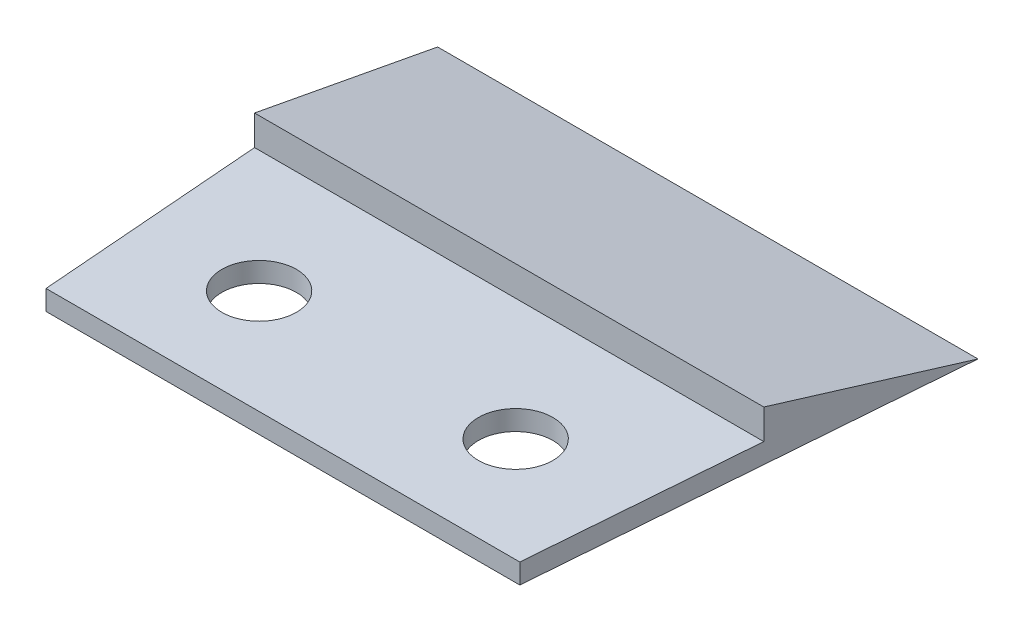
SolidWorks part; units mm, degrees
ref_plane "Front Plane" through (0, 0, 0) normal (0, 0, 1) x (1, 0, 0)
ref_plane "Top Plane" through (0, 0, 0) normal (0, 1, 0) x (1, 0, 0)
ref_plane "Right Plane" through (0, 0, 0) normal (1, 0, 0) x (0, 0, -1)
sketch "Sketch1" plane through (0, 0, 0) normal (0, 1, 0) x (1, 0, 0)
  line L0 (-20.2282, 12.049) -> (21.0214, 12.049)
  line L1 (0.3966, 12.049) -> (0.3966, -20.3868)
  line L2 (-17.6882, -20.3868) -> (18.4814, -20.3868)
  line L3 (-17.6882, -20.3868) -> (-20.2282, 12.049)
  line L4 (18.4814, -20.3868) -> (21.0214, 12.049)
  line L5 (-9.3951, -12.4112) -> (10.1883, -12.4112) construction
  line L6 (-12.1826, -2.5306) -> (12.9759, -2.5306)
  circle A0 centre (-9.3951, -12.4112) radius 2.8448
  circle A1 centre (10.1883, -12.4112) radius 2.8448
  point P8 (0.3966, -12.4112)
  point P13 (0.3966, -2.5306)
  dimension "D6" = 5.6896
  dimension "D1" = 41.2496
  dimension "D2" = 32.4358
  dimension "D3" = 36.1696
  dimension "D4" = 19.5834
  dimension "D5" = 7.9756
  dimension "D7" = 17.8562
extrude "Boss-Extrude1" add sketch "Sketch1" along normal blind 1.524 contours L2 L4 L0 L1 A1 | A0 L1 L0 L3 L2 region at (-9.2904, 0, 3.4513) region at (10.0837, 0, 3.4513)
ref_plane "Plane1" through (0.3966, 0, 0) normal (1, 0, 0) x (0, 0, -1)
sketch "Sketch4" plane through (0.3966, 0, 0) normal (1, 0, 0) x (0, 0, -1)
  line L0 (-3.1148, 1.524) -> (-3.1148, 3.81)
  line L1 (-3.1148, 3.81) -> (12.049, 0)
  line L2 (5.9835, 1.524) -> (12.049, 1.524)
  line L3 (12.049, 1.524) -> (12.049, -0.059)
  line L4 (-20.3868, 0) -> (12.049, 0)
  line L5 (12.049, 0) -> (12.049, 1.524)
  line L6 (12.049, 1.524) -> (-20.3868, 1.524)
  line L7 (-20.3868, 1.524) -> (-20.3868, 0)
  line L8 (-20.3868, 0) -> (12.049, 0)
  line L10 (5.9835, 1.524) -> (-20.3868, 1.524)
  line L11 (-20.3868, 1.524) -> (-20.3868, 0)
  point P2 (-3.1148, 1.524)
  dimension "D2" = 17.272
  dimension "D3" = 3.81
  dimension "D1" = 0
extrude "Boss-Extrude2" add sketch "Sketch4" along normal up to surface and the other way up to surface contours L10 L0 region at (0.3966, 2.286, 0.0821) up to face at (19.7514, 0.762, 4.1689) other way up to face at (-18.9582, 0.762, 4.1689)
extrude "Cut-Extrude1" cut sketch "Sketch4<3>" against normal up to surface and the other way up to surface contours L3 L2 L1 region at (0.3966, 1.016, -10.0271) up to face at (-19.0953, 1.4151, 2.4174) other way up to face at (19.8886, 1.4151, 2.4174)
sketch "Sketch4<3>" plane through (0.3966, 0, 0) normal (1, 0, 0) x (0, 0, -1) same geometry as "Sketch4"
sketch "Sketch5" plane through (0, 0, 0) normal (0, -1, 0) x (1, 0, 0)
  line L0 (0.3966, -12.049) -> (0.3966, 20.3868)
  line L1 (-20.2282, -12.049) -> (21.0214, -12.049) construction
  line L2 (-17.6882, 20.3868) -> (18.4814, 20.3868) construction
sketch "Sketch6" plane through (0, 1.524, 0) normal (0, 1, 0) x (1, 0, 0)
  line L0 (0.3966, 12.049) -> (0.3966, -20.3868) construction
  line L1 (0.3966, 12.049) -> (0.3966, -20.3868)
